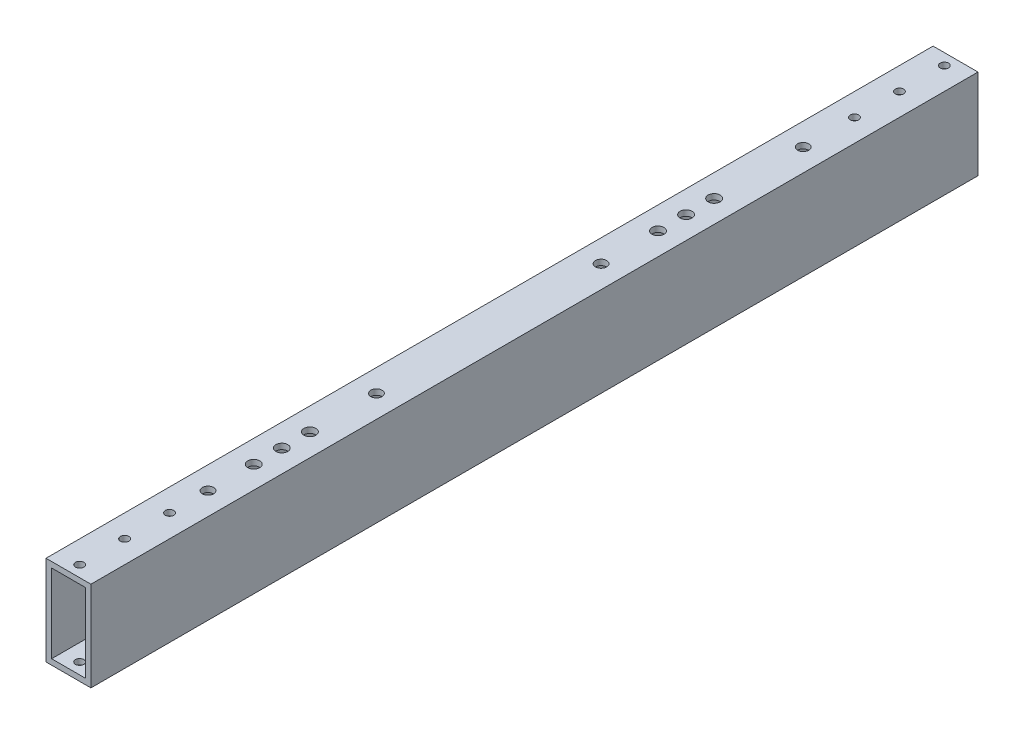
SolidWorks part; units mm, degrees
material "6061-T6 (SS)"
ref_plane "Front Plane" through (0, 0, 0) normal (0, 0, 1) x (1, 0, 0)
ref_plane "Top Plane" through (0, 0, 0) normal (0, 1, 0) x (1, 0, 0)
ref_plane "Right Plane" through (0, 0, 0) normal (1, 0, 0) x (0, 0, -1)
sketch "Sketch1" plane through (0, 0, 0) normal (0, 0, 1) x (1, 0, 0)
  line L1 (-12.7, -25.4) -> (12.7, -25.4)
  line L2 (-12.7, -25.4) -> (-12.7, 25.4)
  line L3 (-12.7, 25.4) -> (12.7, 25.4)
  line L4 (12.7, -25.4) -> (12.7, 25.4)
  line L5 (-12.7, -25.4) -> (12.7, 25.4) construction
  line L6 (-12.7, 25.4) -> (12.7, -25.4) construction
  point P0 (0, 0)
  dimension "D1" = 50.8
  dimension "D2" = 25.4
extrude "Extrude-Thin1" add sketch "Sketch1" along normal blind 501.65 thin thin type one direction reverse wall 3.175
hole_wizard "3/16 (0.1875) Diameter Hole1" positions "3DSketch1" profile "Sketch3" hole size "3/16" standard "ANSI Inch" end condition through all
sketch3d "3DSketch1"
  line L1 (12.7, 25.4, 0) -> (-12.7, 25.4, 0) construction
  line L6 (0, 25.4, 501.65) -> (0, 25.4, 0) construction
  line L7 (12.7, 25.4, 501.65) -> (-12.7, 25.4, 501.65) construction
  point P57 (0, 25.4, 6.35)
  point P59 (0, 25.4, 31.75)
  point P61 (0, 25.4, 57.15)
  point P63 (0, 25.4, 469.9)
  point P65 (0, 25.4, 444.5)
  point P67 (0, 25.4, 495.3)
  dimension "D1" = 25.4
  dimension "D2" = 25.4
  dimension "D3" = 6.35
  dimension "D4" = 25.4
  dimension "D5" = 25.4
  dimension "D6" = 6.35
sketch "Sketch3" plane through (0, 25.4, 495.3) normal (1, 0, 0) x (0, 0, 1)
  line L0 (0, 0) -> (0, 50.8)
  line L1 (0, 50.8) -> (2.3812, 50.8)
  line L2 (2.3812, 50.8) -> (2.3812, 0)
  line L5 (2.3812, 0) -> (0, 0)
  line L11 (0, -6.35) -> (0, 107.95) construction
  dimension "Thru Hole Dia." = 4.7625
  dimension "Thru Hole Depth" = 50.8
hole_wizard "3/16 (0.195) Diameter Hole1" positions "Sketch4" profile "Sketch5" hole size "3/16" standard "ANSI Inch" end condition up to next
sketch "Sketch4" plane through (0, -25.4, 0) normal (0, -1, 0) x (-1, 0, 0)
  point P74 (-3.175, -85.7193)
  point P78 (3.175, -111.1193)
  point P81 (-3.175, -136.5193)
  point P84 (3.175, -161.9193)
  point P87 (-3.175, -187.3193)
  point P90 (3.175, -212.7193)
  point P93 (-3.175, -238.1193)
  point P96 (3.175, -263.5193)
  point P99 (-3.175, -288.9193)
  point P102 (3.175, -314.3193)
  point P105 (-3.175, -339.7193)
  point P108 (3.175, -365.1193)
  point P111 (3.175, -415.9193)
  point P114 (-3.175, -390.5193)
sketch "Sketch5" plane through (3.175, -25.4, 85.7193) normal (1, 0, 0) x (0, 0, -1)
  line L0 (0, 0) -> (0, 3.175)
  line L1 (0, 3.175) -> (2.4765, 3.175)
  line L2 (2.4765, 3.175) -> (2.4765, 0)
  line L5 (2.4765, 0) -> (0, 0)
  line L11 (0, -6.35) -> (0, 107.95) construction
  dimension "Thru Hole Dia." = 4.953
  dimension "Thru Hole Depth" = 3.175
hole_wizard "1/4 (0.25) Diameter Hole1" positions "Sketch6" profile "Sketch7" hole size "1/4" standard "ANSI Inch"
sketch "Sketch6" plane through (0, 25.4, 0) normal (0, 1, 0) x (1, 0, 0)
  point P0 (0, -200.4645)
  point P15 (0, -422.731)
  point P23 (0, -327.481)
  point P26 (0, -86.1545)
sketch "Sketch7" plane through (0, 25.4, 200.4645) normal (1, 0, 0) x (0, 0, 1)
  line L0 (0, 0) -> (0, 27.3077)
  line L1 (0, 27.3077) -> (3.175, 25.4)
  line L2 (3.175, 25.4) -> (3.175, 0)
  line L5 (3.175, 0) -> (0, 0)
  line L10 (0, 27.3077) -> (-3.175, 25.4) construction
  line L11 (0, -6.35) -> (0, 107.95) construction
  dimension "Hole Dia." = 6.35
  dimension "Hole Depth" = 25.4
  dimension "Drill Angle" = 118
hole_wizard "1/4 Clearance Hole1" positions "Sketch17" profile "Sketch18" hole size "1/4" standard "ANSI Inch"
sketch "Sketch17" plane through (-381, 25.4, 250.825) normal (0, 1, 0) x (1, 0, 0)
  point P0 (381, 82.55)
  point P3 (381, 98.425)
  point P6 (381, 114.3)
  point P9 (381, -146.05)
  point P12 (381, -130.175)
  point P15 (381, -114.3)
  point P18 (-381, -146.05)
  point P21 (-381, -130.175)
  point P24 (-381, -114.3)
  point P27 (-381, 82.55)
  point P30 (-381, 98.425)
  point P33 (-381, 114.3)
sketch "Sketch18" plane through (0, 25.4, 168.275) normal (1, 0, 0) x (0, 0, 1)
  line L0 (0, 0) -> (0, 40.1298)
  line L1 (0, 40.1298) -> (3.3782, 38.1)
  line L2 (3.3782, 38.1) -> (3.3782, 0)
  line L3 (3.3782, 0) -> (0, 0)
  line L4 (0, 40.1298) -> (-3.3782, 38.1) construction
  line L5 (0, -6.35) -> (0, 107.95) construction
  dimension "Hole Dia." = 6.7564
  dimension "Hole Depth" = 38.1
  dimension "Drill Angle" = 118
